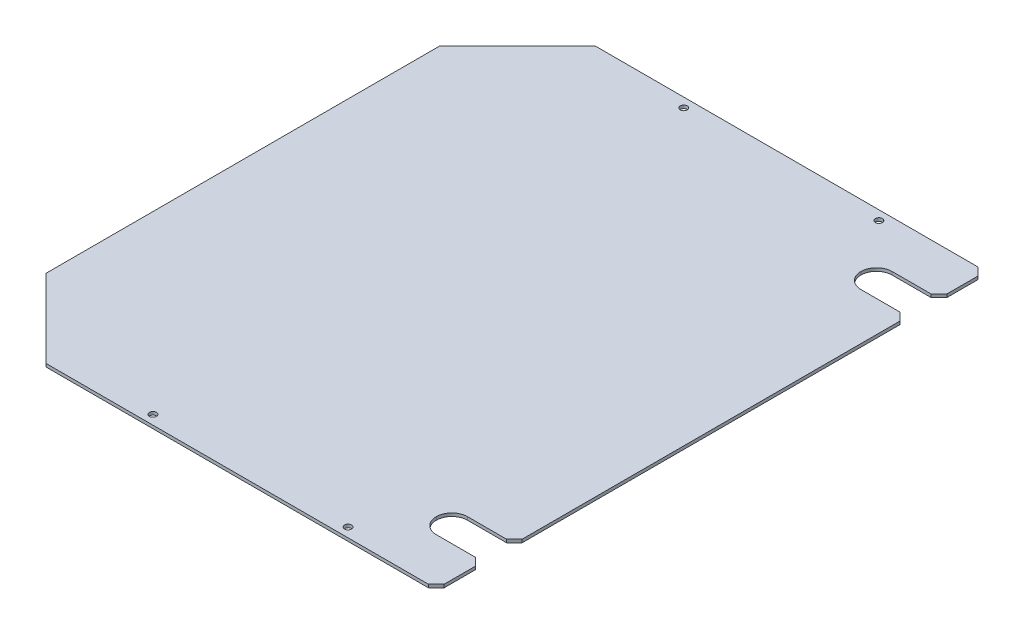
SolidWorks part; units mm, degrees
material "1060 Alloy"
ref_plane "Front Plane" through (0, 0, 0) normal (0, 0, 1) x (1, 0, 0)
ref_plane "Top Plane" through (0, 0, 0) normal (0, 1, 0) x (1, 0, 0)
ref_plane "Right Plane" through (0, 0, 0) normal (1, 0, 0) x (0, 0, -1)
sketch "Sketch1" plane through (0, 0, 0) normal (0, 0, 1) x (1, 0, 0)
  line L0 (-150, 0) -> (150, 0)
  dimension "D1" = 300
sheet metal parameters "Sheet-Metal1" thickness 2 parameters "D1"=2
base flange "Base-Flange1" sketch "Sketch1" end condition blind depth 352 reverse direction no thickness 2 reverse thickness direction no bend radius 2
chamfer "Chamfer1" distance 5 angle 45 2 edges at (150, -1, 0) (150, -1, 352)
chamfer "Chamfer2" distance 50 angle 45 2 edges at (-150, -1, 352) (-150, -1, 0)
sketch "Sketch2" plane through (0, -2, 0) normal (0, -1, 0) x (1, 0, 0)
  circle A0 centre (-37.5, 346) radius 2.25
  circle A1 centre (87.5, 346) radius 2.25
  circle A2 centre (87.5, 6) radius 2.25
  circle A3 centre (-37.5, 6) radius 2.25
  dimension "D1" = 4.5
extrude "Cut-Extrude1" cut sketch "Sketch2" against normal up to next normal cut yes
sketch "Sketch3" plane through (0, 0, 0) normal (0, 1, 0) x (1, 0, 0)
  line L0 (150, -347) -> (150, -5) construction
  line L1 (150, -30) -> (110, -30)
  line L2 (150, -30) -> (150, -50)
  line L3 (150, -50) -> (110, -50)
  line L4 (110, -30) -> (110, -50)
  line L5 (-150, -176) -> (150, -176) construction
  line L6 (-150, -302) -> (-150, -50) construction
  line L7 (110, -322) -> (110, -302)
  line L8 (150, -302) -> (110, -302)
  line L9 (150, -322) -> (150, -302)
  line L10 (150, -322) -> (110, -322)
  dimension "D1" = 20
  dimension "D2" = 252
  dimension "D3" = 40
extrude "Cut-Extrude2" cut sketch "Sketch3" against normal through all normal cut yes
fillet "Fillet1" radius 10 4 edges at (110, -1, 322) (110, -1, 302) (110, -1, 50) (110, -1, 30)
chamfer "Chamfer3" distance 5 angle 45 4 edges at (150, -1, 322) (150, -1, 302) (150, -1, 50) (150, -1, 30)
flat pattern "Flat-Pattern1" [suppressed]
sketch "Bend-Lines1" plane through (0, 0, 0) normal (0, 1, 0) x (-1, 0, 0)
